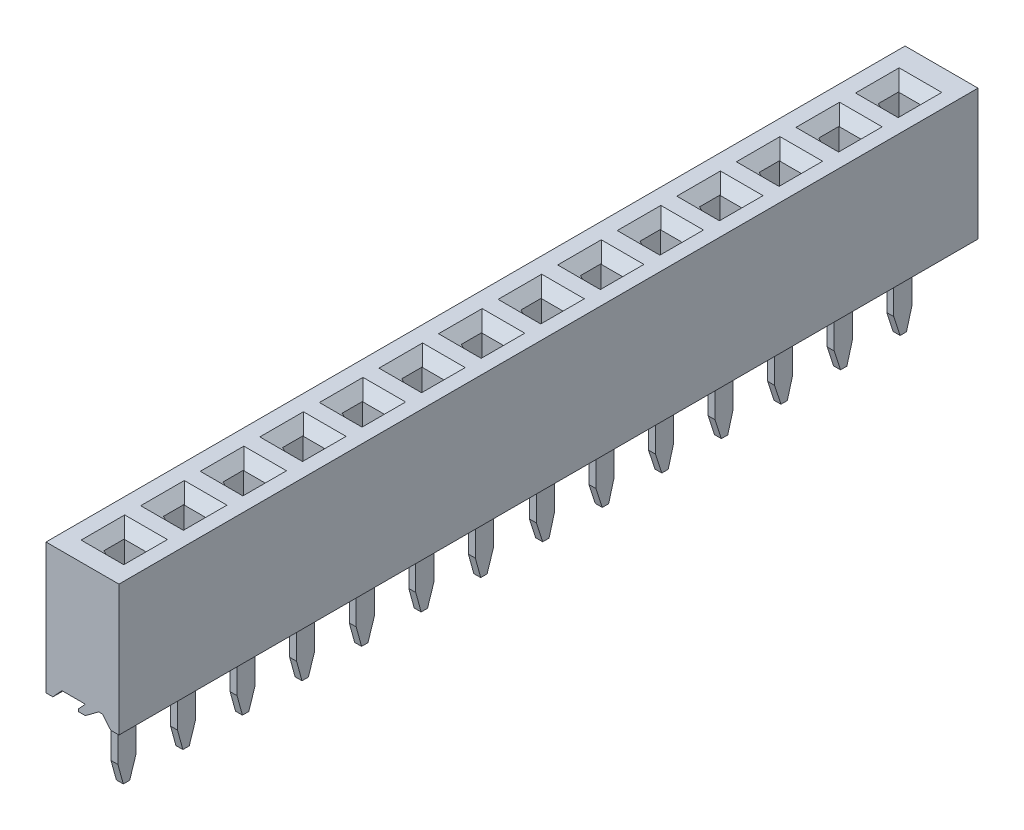
SolidWorks part; units mm, degrees
ref_plane "Front" through (0, 0, 0) normal (0, 0, 1) x (1, 0, 0)
ref_plane "Top" through (0, 0, 0) normal (0, 1, 0) x (1, 0, 0)
ref_plane "Right" through (0, 0, 0) normal (1, 0, 0) x (0, 0, -1)
sketch "Эскиз1" plane through (0, 0, 0) normal (1, 0, 0) x (0, 0, -1)
  line L0 (27.3847, 79.0408) -> (53.3847, 79.0408) construction
  line L47 (3.7406, 8.2112) -> (3.7406, 12.5112) construction
  line L91 (1.3664, 8.1719) -> (1.3664, 12.4719)
  line L92 (15.4992, 8.1719) -> (15.4992, 12.4719)
  line L93 (1.3664, 12.4719) -> (29.6319, 12.4719)
  line L94 (1.3664, 8.1719) -> (2.4375, 8.1719)
  line L95 (2.4375, 8.1719) -> (2.4375, 6.2446)
  line L96 (2.4375, 6.2446) -> (2.6149, 5.5996)
  line L97 (2.6149, 5.5996) -> (2.8245, 5.5996)
  line L98 (2.8245, 5.5996) -> (3.0342, 6.2446)
  line L99 (3.0342, 6.2446) -> (3.0342, 8.1719)
  line L100 (3.0342, 8.1719) -> (4.3975, 8.1719)
  line L101 (4.3975, 8.1719) -> (4.3975, 6.2446)
  line L102 (4.3975, 6.2446) -> (4.5749, 5.5996)
  line L103 (4.5749, 5.5996) -> (4.7845, 5.5996)
  line L104 (4.7845, 5.5996) -> (4.9942, 6.2446)
  line L105 (4.9942, 6.2446) -> (4.9942, 8.1719)
  line L106 (4.9942, 8.1719) -> (6.3575, 8.1719)
  line L107 (6.3575, 8.1719) -> (6.3575, 6.2446)
  line L108 (6.3575, 6.2446) -> (6.5349, 5.5996)
  line L109 (6.5349, 5.5996) -> (6.7445, 5.5996)
  line L110 (6.7445, 5.5996) -> (6.9542, 6.2446)
  line L111 (6.9542, 6.2446) -> (6.9542, 8.1719)
  line L112 (6.9542, 8.1719) -> (8.3175, 8.1719)
  line L113 (8.3175, 8.1719) -> (8.3175, 6.2446)
  line L114 (8.3175, 6.2446) -> (8.4949, 5.5996)
  line L115 (8.4949, 5.5996) -> (8.7045, 5.5996)
  line L116 (8.7045, 5.5996) -> (8.9142, 6.2446)
  line L117 (8.9142, 6.2446) -> (8.9142, 8.1719)
  line L118 (8.9142, 8.1719) -> (10.2775, 8.1719)
  line L119 (10.2775, 8.1719) -> (10.2775, 6.2446)
  line L120 (10.2775, 6.2446) -> (10.4549, 5.5996)
  line L121 (10.4549, 5.5996) -> (10.6645, 5.5996)
  line L122 (10.6645, 5.5996) -> (10.8742, 6.2446)
  line L123 (10.8742, 6.2446) -> (10.8742, 8.1719)
  line L124 (10.8742, 8.1719) -> (12.2375, 8.1719)
  line L125 (12.2375, 8.1719) -> (12.2375, 6.2446)
  line L126 (12.2375, 6.2446) -> (12.4149, 5.5996)
  line L127 (12.4149, 5.5996) -> (12.6245, 5.5996)
  line L128 (12.6245, 5.5996) -> (12.8342, 6.2446)
  line L129 (12.8342, 6.2446) -> (12.8342, 8.1719)
  line L130 (12.8342, 8.1719) -> (14.1975, 8.1719)
  line L131 (14.1975, 8.1719) -> (14.1975, 6.2446)
  line L132 (14.1975, 6.2446) -> (14.3749, 5.5996)
  line L133 (14.3749, 5.5996) -> (14.5845, 5.5996)
  line L134 (14.5845, 5.5996) -> (14.7942, 6.2446)
  line L135 (14.7942, 6.2446) -> (14.7942, 8.1719)
  line L136 (14.7942, 8.1719) -> (16.2041, 8.1719)
  line L137 (14.7942, 8.1719) -> (16.1575, 8.1719) [skipped]
  line L138 (16.2041, 6.2446) -> (16.2041, 8.1719)
  line L139 (16.4138, 5.5996) -> (16.2041, 6.2446)
  line L140 (16.6234, 5.5996) -> (16.4138, 5.5996)
  line L141 (16.8008, 6.2446) -> (16.6234, 5.5996)
  line L142 (16.8008, 8.1719) -> (16.8008, 6.2446)
  line L143 (18.1641, 8.1719) -> (16.8008, 8.1719)
  line L144 (18.1641, 6.2446) -> (18.1641, 8.1719)
  line L145 (18.3738, 5.5996) -> (18.1641, 6.2446)
  line L146 (18.5834, 5.5996) -> (18.3738, 5.5996)
  line L147 (18.7608, 6.2446) -> (18.5834, 5.5996)
  line L148 (18.7608, 8.1719) -> (18.7608, 6.2446)
  line L149 (20.1241, 8.1719) -> (18.7608, 8.1719)
  line L150 (20.1241, 6.2446) -> (20.1241, 8.1719)
  line L151 (20.3338, 5.5996) -> (20.1241, 6.2446)
  line L152 (20.5434, 5.5996) -> (20.3338, 5.5996)
  line L153 (20.7208, 6.2446) -> (20.5434, 5.5996)
  line L154 (20.7208, 8.1719) -> (20.7208, 6.2446)
  line L155 (22.0841, 8.1719) -> (20.7208, 8.1719)
  line L156 (22.0841, 6.2446) -> (22.0841, 8.1719)
  line L157 (22.2938, 5.5996) -> (22.0841, 6.2446)
  line L158 (22.5034, 5.5996) -> (22.2938, 5.5996)
  line L159 (22.6808, 6.2446) -> (22.5034, 5.5996)
  line L160 (22.6808, 8.1719) -> (22.6808, 6.2446)
  line L161 (24.0441, 8.1719) -> (22.6808, 8.1719)
  line L162 (24.0441, 6.2446) -> (24.0441, 8.1719)
  line L163 (24.2538, 5.5996) -> (24.0441, 6.2446)
  line L164 (24.4634, 5.5996) -> (24.2538, 5.5996)
  line L165 (24.6408, 6.2446) -> (24.4634, 5.5996)
  line L166 (24.6408, 8.1719) -> (24.6408, 6.2446)
  line L167 (26.0041, 8.1719) -> (24.6408, 8.1719)
  line L168 (26.0041, 6.2446) -> (26.0041, 8.1719)
  line L169 (26.2138, 5.5996) -> (26.0041, 6.2446)
  line L170 (26.4234, 5.5996) -> (26.2138, 5.5996)
  line L171 (26.6008, 6.2446) -> (26.4234, 5.5996)
  line L172 (26.6008, 8.1719) -> (26.6008, 6.2446)
  line L173 (27.9641, 8.1719) -> (26.6008, 8.1719)
  line L174 (27.9641, 6.2446) -> (27.9641, 8.1719)
  line L175 (28.1738, 5.5996) -> (27.9641, 6.2446)
  line L176 (28.3834, 5.5996) -> (28.1738, 5.5996)
  line L177 (28.5608, 6.2446) -> (28.3834, 5.5996)
  line L178 (28.5608, 8.1719) -> (28.5608, 6.2446)
  line L179 (29.6319, 8.1719) -> (28.5608, 8.1719)
  line L180 (29.6319, 8.1719) -> (29.6319, 12.4719)
  point P8 (14.7992, 7.196)
  point P9 (16.1764, 7.196)
  dimension "D1" = 26
  dimension "D2" = 4.3
  dimension "D3" = 4.3
  dimension "D4" = 0.7
  dimension "D5" = 7
extrude "Бобышка-Вытянуть2" add sketch "Эскиз1" along normal mid plane 2.4 contours L135 L136 L92 L93 L91 L94 L95 L96 L97 L98 L99 L100 L101 L102 L103 L104 L105 L106 L107 L108 L109 L110 L111 L112 L113 L114 L115 L116 L117 L118 L119 L120 L121 L122 L123 L124 L125 L126 L127 L128 L129 L130 L131 L132 L133 L134 | L179 L180 L93 L92 L136 L138 L139 L140 L141 L142 L143 L144 L145 L146 L147 L148 L149 L150 L151 L152 L153 L154 L155 L156 L157 L158 L159 L160 L161 L162 L163 L164 L165 L166 L167 L168 L169 L170 L171 L172 L173 L174 L175 L176 L177 L178 region at (0, 9.8551, -8.4582) region at (0, 9.8551, -22.5401)
sketch "Эскиз4" plane through (0, 0, -1.3664) normal (0, 0, 1) x (1, 0, 0)
  line L0 (-1.2157, 8.1983) -> (-1.2157, 12.4983) construction
  line L1 (1.2, 8.1719) -> (0.9319, 8.1719)
  line L3 (1.2, 8.1719) -> (-1.2, 8.1719) construction
  line L4 (0.9319, 8.1719) -> (0.6602, 8.4978)
  line L5 (0.6602, 8.4978) -> (0.5353, 8.4978)
  line L6 (0.5353, 8.4978) -> (0.0947, 8.1719)
  line L7 (0.0947, 8.1719) -> (0.0947, 5.5996)
  line L8 (1.2, 5.5996) -> (-1.2, 5.5996) construction
  line L10 (-0.133, 5.5996) -> (-0.133, 8.2481)
  line L11 (-0.133, 8.2481) -> (0.0947, 8.4978)
  line L12 (0.0947, 8.4978) -> (-0.6764, 8.4978)
  line L13 (-0.6764, 8.4978) -> (-0.9736, 8.1719)
  line L14 (-0.9736, 8.1719) -> (-1.2, 8.1719)
  line L15 (-1.2, 8.1719) -> (-1.2, 5.5996)
  line L16 (-1.2, 5.5996) -> (-0.133, 5.5996)
  line L17 (1.2, 8.1719) -> (1.2, 5.5996)
  line L18 (1.2, 5.5996) -> (0.0947, 5.5996)
  dimension "D1" = 4.3
extrude "Вырез-Вытянуть1" cut sketch "Эскиз4" against normal through all
sketch "Эскиз5" plane through (0, 12.4719, 0) normal (0, 1, 0) x (1, 0, 0)
  line L0 (2.9085, 2.8734) -> (2.9085, 4.8734) construction
  line L1 (-0.6764, 29.6319) -> (-0.6764, 1.3664) construction
  line L2 (-0.6764, 3.4327) -> (0.7268, 3.4327)
  line L3 (-0.6764, 3.4327) -> (-0.6764, 1.9985)
  line L4 (-0.6764, 1.9985) -> (0.7268, 1.9985)
  line L5 (0.7268, 3.4327) -> (0.7268, 1.9985)
  line L7 (-0.3371, 3.0826) -> (0.3632, 3.0826)
  line L8 (-0.3371, 3.0826) -> (-0.3371, 2.4093)
  line L9 (-0.3371, 2.4093) -> (0.3632, 2.4093)
  line L10 (0.3632, 3.0826) -> (0.3632, 2.4093)
  dimension "D1" = 2
extrude "Вырез-Вытянуть2" cut sketch "Эскиз5" against normal blind 2.4 draft 45 contours L5 L4 L3 L2
extrude "Вырез-Вытянуть3" cut sketch "Эскиз5<3>" against normal blind 2.4 contours L10 L7 L8 L9 region at (0.0131, 12.4719, -2.7459)
sketch "Эскиз5<3>" plane through (0, 12.4719, 0) normal (0, 1, 0) x (1, 0, 0) same geometry as "Эскиз5"
pattern_linear "Линейный массив1" count 14 spacing 1.96 along (0, 0, -1) of "Вырез-Вытянуть2", "Вырез-Вытянуть3"
